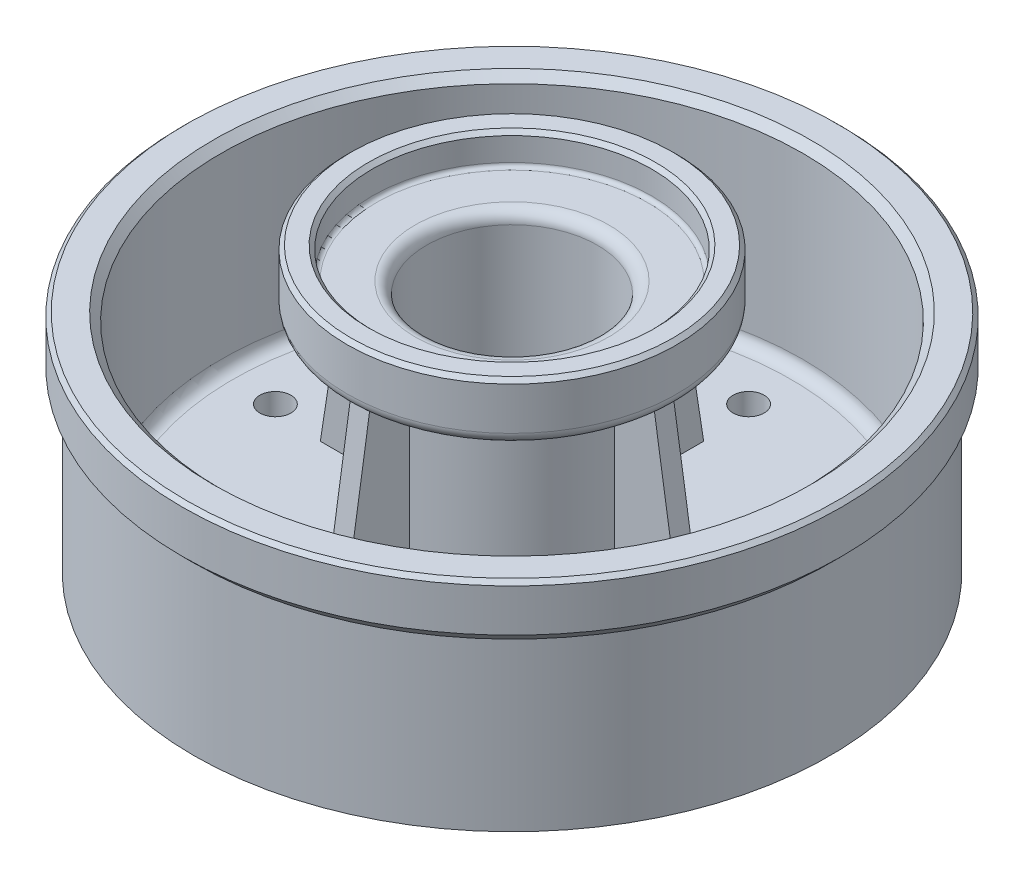
SolidWorks part; units mm, degrees
material "Plain Carbon Steel"
ref_plane "Front Plane" through (0, 0, 0) normal (0, 0, 1) x (1, 0, 0)
ref_plane "Top Plane" through (0, 0, 0) normal (0, 1, 0) x (1, 0, 0)
ref_plane "Right Plane" through (0, 0, 0) normal (1, 0, 0) x (0, 0, -1)
sketch "Sketch2" plane through (0, 0, 0) normal (0, 1, 0) x (1, 0, 0)
  circle A0 centre (0, 0) radius 82
  dimension "D1" = 164
extrude "Boss-Extrude1" add sketch "Sketch2" along normal blind 43
sketch "Sketch3" plane through (0, 43, 0) normal (0, 1, 0) x (1, 0, 0)
  circle A0 centre (0, 0) radius 85
extrude "Boss-Extrude2" add sketch "Sketch3" along normal blind 15
sketch "Sketch4" plane through (0, 58, 0) normal (0, 1, 0) x (1, 0, 0)
  circle A0 centre (0, 0) radius 75
  dimension "D1" = 150
extrude "Cut-Extrude1" cut sketch "Sketch4" against normal blind 51
sketch "Sketch5" plane through (0, 7, 0) normal (0, 1, 0) x (1, 0, 0)
  circle A0 centre (0, 0) radius 29
  dimension "D1" = 58
extrude "Boss-Extrude3" add sketch "Sketch5" along normal blind 51
sketch "Sketch6" plane through (0, 58, 0) normal (0, 1, 0) x (1, 0, 0)
  circle A0 centre (0, 0) radius 42.5
  dimension "D1" = 85
extrude "Boss-Extrude4" add sketch "Sketch6" along normal blind 15
sketch "Sketch7" plane through (0, 73, 0) normal (0, 1, 0) x (1, 0, 0)
  circle A0 centre (0, 0) radius 36
  circle A2 centre (0, 0) radius 22
  dimension "D1" = 72
  dimension "D2" = 44
extrude "Cut-Extrude6" cut sketch "Sketch7" against normal blind 8 contours A0
extrude "Cut-Extrude7" cut sketch "Sketch7<5>" against normal through all contours A2 region at (0, 73, 0)
sketch "Sketch7<5>" plane through (0, 73, 0) normal (0, 1, 0) x (1, 0, 0) same geometry as "Sketch7"
chamfer "Chamfer1" distance 1 angle 45 3 edges at (0, 58, 85) (0, 73, 42.5) (0, 73, 36)
chamfer "Chamfer2" distance 2 angle 45 1 edges at (0, 58, 75)
fillet "Fillet1" radius 3 6 edges at (0, 7, 29) (0, 58, 29) (0, 0, 22) (0, 65, 22) (0, 7, 75) (0, 58, 42.5)
chamfer "Chamfer3" distance 3 angle 45 1 edges at (0, 43, 85)
fillet "Fillet2" radius 1 1 edges at (0, 65, 36)
sketch "Sketch9" plane through (0, 0, 0) normal (0, 0, 1) x (1, 0, 0)
  line L0 (0, 0) -> (-48, 0)
  line L1 (-48, 0) -> (-39, 58.104)
  line L2 (-39, 58.104) -> (0, 58)
  line L3 (77, 58) -> (-77, 58) construction
  line L4 (0, 58) -> (0, 0)
  dimension "D1" = 48
  dimension "D2" = 39
sketch "Sketch10" plane through (0, 0, 0) normal (0, 1, 0) x (1, 0, 0)
  line L0 (-48, 0) -> (-48, 17.9883)
  line L1 (0, 0) -> (-48, 0) construction
ref_plane "Plane1" through (-46.8754, 7.2607, 0) normal (0.9882, -0.1531, 0) x (0, 0, -1)
sketch "Sketch11" plane through (-46.8754, 7.2607, 0) normal (0.9882, -0.1531, 0) x (0, 0, -1)
  line L0 (2.5, -1.3915) -> (-2.5, -1.3915)
  line L1 (2.5, -1.3915) -> (2.5, 56.0572)
  line L2 (2.5, 56.0572) -> (-2.5, 56.0572)
  line L3 (-2.5, 56.0572) -> (-2.5, -1.3915)
  line L5 (0, 0) -> (0, 70.2358) construction
  line L6 (0, 70.2358) -> (0, -19.1524) construction
  dimension "D1" = 5
  dimension "D2" = 2.5
extrude "Boss-Extrude8" add sketch "Sketch11" along normal up to surface (18.4133 mm away) up to face at (0, 10, 29)
pattern_circular "CirPattern2" count 4 over 360 about axis through (0, 58, 0) along (0, -1, 0) of "Boss-Extrude8" reverse direction yes
sketch "Sketch16" plane through (0, 7, 0) normal (0, 1, 0) x (1, 0, 0)
  line L0 (0, 0) -> (-105.2266, 0) construction
  circle A0 centre (-61, 0) radius 4
  circle A1 centre (-43.1335, 43.1335) radius 4
  circle A2 centre (0, 61) radius 4
  circle A3 centre (43.1335, 43.1335) radius 4
  circle A4 centre (61, 0) radius 4
  circle A5 centre (43.1335, -43.1335) radius 4
  circle A6 centre (0, -61) radius 4
  circle A7 centre (-43.1335, -43.1335) radius 4
  point P22 (0, 0)
  dimension "D1" = 61
  dimension "D2" = 8
  dimension "D3" = 8
extrude "Cut-Extrude9" cut sketch "Sketch16" against normal through all
